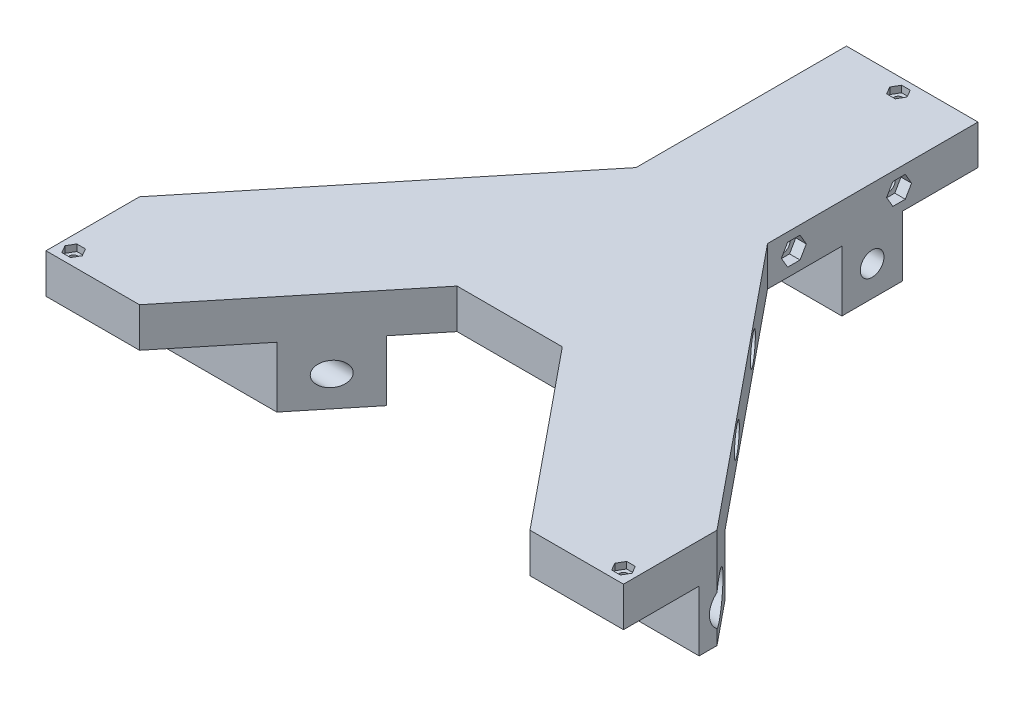
SolidWorks part; units mm, degrees
ref_plane "Front Plane" through (0, 0, 0) normal (0, 0, 1) x (1, 0, 0)
ref_plane "Top Plane" through (0, 0, 0) normal (0, 1, 0) x (1, 0, 0)
ref_plane "Right Plane" through (0, 0, 0) normal (1, 0, 0) x (0, 0, -1)
sketch "Sketch1" plane through (0, 0, 0) normal (0, 1, 0) x (1, 0, 0)
  line L0 (0, 0) -> (0, 143741.8209) construction
  line L1 (25, 0) -> (-25, 0)
  line L2 (-25, 0) -> (-25, -80)
  line L3 (25, 0) -> (25, -80)
  line L4 (-25, -80) -> (-109.75, -183.9619)
  line L5 (25, -80) -> (109.75, -183.9619)
  line L6 (-109.75, -183.9619) -> (-109.75, -219.5)
  line L7 (109.75, -183.9619) -> (109.75, -219.5)
  line L8 (-109.75, -219.5) -> (-74.2119, -219.5)
  line L9 (109.75, -219.5) -> (74.2119, -219.5)
  line L10 (-74.2119, -219.5) -> (-20, -152.9988)
  line L11 (74.2119, -219.5) -> (20, -152.9988)
  line L12 (-20, -152.9988) -> (20, -152.9988)
  point P6 (0, 0)
  point P16 (0, -152.9988)
  point P17 (82.4843, -217.5)
  point P18 (25.4247, -96.6746)
  point P19 (28.6457, -80.0329)
  point P20 (34.5508, -158.9467)
  point P21 (-30, -75.5085)
  point P22 (25, -66.3731)
  point P23 (19.1505, -153.0497)
  dimension "D1" = 219.5
  dimension "D2" = 219.5
  dimension "D3" = 50
  dimension "D4" = 50
  dimension "D5" = 80
  dimension "D6" = 40
extrude "Boss-Extrude1" add sketch "Sketch1" along normal blind 15
sketch "Sketch4" plane through (-109.75, 0, 0) normal (-1, 0, 0) x (0, 0, 1)
  line L0 (0, 15) -> (0, 0) construction
  line L1 (80, 15) -> (80, 0) construction
  line L2 (152.9988, 15) -> (152.9988, 0) construction
  circle A0 centre (30, 7.5) radius 2.55
  circle A1 centre (70, 7.5) radius 2.55
  circle A2 centre (110, 7.5) radius 2.55
  circle A3 centre (142.9988, 7.5) radius 2.55
  point P10 (0, 7.5)
  dimension "D1" = 5.1
  dimension "D2" = 30
  dimension "D3" = 10
  dimension "D4" = 30
  dimension "D5" = 10
extrude "Cut-Extrude1" cut sketch "Sketch4" against normal through all
sketch "Sketch5" plane through (-25, 0, 0) normal (-1, 0, 0) x (0, 0, 1)
  circle A0 centre (30, 7.5) radius 4.25
  circle A1 centre (70, 7.5) radius 4.25
  circle A2 centre (110, 7.5) radius 4.25
  circle A3 centre (142.9988, 7.5) radius 4.25
  dimension "D1" = 8.5
extrude "Cut-Extrude3" cut sketch "Sketch5" against normal blind 3.5 and the other way through all
sketch "Sketch6" plane through (25, 0, 0) normal (1, 0, 0) x (0, 0, -1)
  circle A0 centre (-142.9988, 7.5) radius 5
  circle A1 centre (-110, 7.5) radius 5
  dimension "D1" = 10
  dimension "D2" = 10
extrude "Cut-Extrude4" cut sketch "Sketch6" along normal through all
sketch "Sketch7" plane through (25, 0, 0) normal (1, 0, 0) x (0, 0, -1)
  line L1 (-34.7343, 7.5) -> (-32.3671, 3.4)
  line L2 (-32.3671, 3.4) -> (-27.6329, 3.4)
  line L3 (-27.6329, 3.4) -> (-25.2657, 7.5)
  line L4 (-25.2657, 7.5) -> (-27.6329, 11.6)
  line L5 (-27.6329, 11.6) -> (-32.3671, 11.6)
  line L6 (-32.3671, 11.6) -> (-34.7343, 7.5)
  line L7 (-74.7343, 7.5) -> (-72.3671, 3.4)
  line L8 (-72.3671, 3.4) -> (-67.6329, 3.4)
  line L9 (-67.6329, 3.4) -> (-65.2657, 7.5)
  line L10 (-65.2657, 7.5) -> (-67.6329, 11.6)
  line L11 (-67.6329, 11.6) -> (-72.3671, 11.6)
  line L12 (-72.3671, 11.6) -> (-74.7343, 7.5)
  line L13 (-114.7343, 7.5) -> (-112.3671, 3.4)
  line L14 (-112.3671, 3.4) -> (-107.6329, 3.4)
  line L15 (-107.6329, 3.4) -> (-105.2657, 7.5)
  line L16 (-105.2657, 7.5) -> (-107.6329, 11.6)
  line L17 (-107.6329, 11.6) -> (-112.3671, 11.6)
  line L18 (-112.3671, 11.6) -> (-114.7343, 7.5)
  line L19 (-147.7331, 7.5) -> (-145.366, 3.4)
  line L20 (-145.366, 3.4) -> (-140.6317, 3.4)
  line L21 (-140.6317, 3.4) -> (-138.2646, 7.5)
  line L22 (-138.2646, 7.5) -> (-140.6317, 11.6)
  line L23 (-140.6317, 11.6) -> (-145.366, 11.6)
  line L24 (-145.366, 11.6) -> (-147.7331, 7.5)
  circle A0 centre (-30, 7.5) radius 4.1 construction
  circle A1 centre (-70, 7.5) radius 4.1 construction
  circle A2 centre (-110, 7.5) radius 4.1 construction
  circle A3 centre (-142.9988, 7.5) radius 4.1 construction
  point P28 (0, 0)
  point P37 (0, 0)
  point P38 (0, 0)
  dimension "D1" = 8.2
extrude "Cut-Extrude5" cut sketch "Sketch7" against normal blind 4
sketch "Sketch8" plane through (0, 15, 0) normal (0, 1, 0) x (1, 0, 0)
  line L0 (25, 0) -> (-25, 0) construction
  line L1 (-109.75, -219.5) -> (-74.2119, -219.5) construction
  line L3 (-109.75, -183.9619) -> (-109.75, -219.5) construction
  line L4 (109.75, -219.5) -> (109.75, -183.9619) construction
  circle A0 centre (0, -5.25) radius 1.6
  circle A1 centre (-104.5, -214.25) radius 1.6
  circle A2 centre (104.5, -214.25) radius 1.6
  point P13 (0, 0)
  point P15 (0, 0)
  dimension "D1" = 3.2
  dimension "D3" = 5.25
  dimension "D2" = 5.25
  dimension "D4" = 5.25
  dimension "D5" = 5.25
extrude "Cut-Extrude6" cut sketch "Sketch8" against normal through all
sketch "Sketch9" plane through (0, 15, 0) normal (0, 1, 0) x (1, 0, 0)
  line L1 (-101.2091, -214.25) -> (-102.8546, -211.4)
  line L2 (-102.8546, -211.4) -> (-106.1454, -211.4)
  line L3 (-106.1454, -211.4) -> (-107.7909, -214.25)
  line L4 (-107.7909, -214.25) -> (-106.1454, -217.1)
  line L5 (-106.1454, -217.1) -> (-102.8546, -217.1)
  line L6 (-102.8546, -217.1) -> (-101.2091, -214.25)
  line L7 (101.2091, -214.25) -> (102.8546, -217.1)
  line L8 (102.8546, -217.1) -> (106.1454, -217.1)
  line L9 (106.1454, -217.1) -> (107.7909, -214.25)
  line L10 (107.7909, -214.25) -> (106.1454, -211.4)
  line L11 (106.1454, -211.4) -> (102.8546, -211.4)
  line L12 (102.8546, -211.4) -> (101.2091, -214.25)
  line L13 (3.2909, -5.25) -> (1.6454, -2.4)
  line L14 (1.6454, -2.4) -> (-1.6454, -2.4)
  line L15 (-1.6454, -2.4) -> (-3.2909, -5.25)
  line L16 (-3.2909, -5.25) -> (-1.6454, -8.1)
  line L17 (-1.6454, -8.1) -> (1.6454, -8.1)
  line L18 (1.6454, -8.1) -> (3.2909, -5.25)
  circle A0 centre (-104.5, -214.25) radius 2.85 construction
  circle A1 centre (104.5, -214.25) radius 2.85 construction
  circle A2 centre (0, -5.25) radius 2.85 construction
  point P1 (0, 0)
  dimension "D1" = 5.7
  dimension "D2" = 5.7
  dimension "D3" = 5.7
extrude "Cut-Extrude7" cut sketch "Sketch9" against normal blind 2.5
sketch "Sketch10" plane through (0, 0, 0) normal (0, -1, 0) x (1, 0, 0)
  line L0 (6.2244, 40.25) -> (-49993.7756, 40.25) construction
  line L1 (84.4314, 179.25) -> (-49915.5686, 179.25) construction
  line L2 (7.3106, 36.25) -> (-49992.6894, 36.25) construction
  line L3 (6.2244, 44.25) -> (-49993.7756, 44.25) construction
  line L4 (67.052, 175.25) -> (-49932.948, 175.25) construction
  line L5 (77.9141, 183.25) -> (-49922.0859, 183.25) construction
  line L6 (25, 0) -> (-25, 0) construction
  line L7 (74.2119, 219.5) -> (109.75, 219.5) construction
  line L8 (-25, 0) -> (-25, 80) construction
  line L9 (25, 51.75) -> (-25, 51.75)
  line L10 (25, 51.75) -> (25, 28.75)
  line L11 (25, 28.75) -> (-25, 28.75)
  line L12 (-25, 51.75) -> (-25, 28.75)
  line L13 (25, 51.75) -> (-25, 28.75) construction
  line L14 (25, 28.75) -> (-25, 51.75) construction
  line L15 (25, 80) -> (25, 0) construction
  line L16 (96.534, 167.75) -> (32.0252, 167.75)
  line L17 (109.75, 183.9619) -> (25, 80) construction
  line L18 (20, 152.9988) -> (74.2119, 219.5) construction
  line L19 (32.0252, 167.75) -> (50.7748, 190.75)
  line L20 (50.7748, 190.75) -> (109.75, 190.75)
  line L21 (109.75, 219.5) -> (109.75, 183.9619) construction
  line L22 (109.75, 190.75) -> (109.75, 183.9619)
  line L23 (109.75, 183.9619) -> (96.534, 167.75)
  line L24 (0, 0) -> (0, -50000) construction
  line L25 (-109.75, 190.75) -> (-109.75, 183.9619)
  line L26 (-50.7748, 190.75) -> (-109.75, 190.75)
  line L27 (-32.0252, 167.75) -> (-50.7748, 190.75)
  line L28 (-96.534, 167.75) -> (-32.0252, 167.75)
  line L29 (-109.75, 183.9619) -> (-96.534, 167.75)
  point P16 (0, 40.25)
  dimension "D1" = 40.25
  dimension "D2" = 40.25
  dimension "D3" = 4
  dimension "D4" = 4
  dimension "D5" = 4
  dimension "D6" = 4
  dimension "D7" = 23
  dimension "D8" = 23
  dimension "D9" = 11.5
extrude "Boss-Extrude2" add sketch "Sketch10" along normal blind 23
ref_plane "Plane1" through (-96.534, 0, 0) normal (-1, 0, 0) x (0, 0, 1)
sketch "Sketch11" plane through (-96.534, 0, 0) normal (-1, 0, 0) x (0, 0, 1)
  line L0 (167.75, -23) -> (167.75, 0) construction
  line L1 (183.9619, -23) -> (167.75, -23) construction
  circle A0 centre (179.25, -11.5) radius 7.6
  point P6 (176.6753, -17.2283)
  dimension "D2" = 11.5
  dimension "D3" = 15.2
  dimension "D1" = 11.5
extrude "Cut-Extrude8" cut sketch "Sketch11" against normal blind 24 and the other way through all
sketch "Sketch12" plane through (-96.534, 0, 0) normal (-1, 0, 0) x (0, 0, 1)
  circle A0 centre (179.25, -11.5) radius 4.5
  dimension "D1" = 9
extrude "Cut-Extrude9" cut sketch "Sketch12" against normal through all
mirror "Mirror1" about plane through (0, 0, 0) normal (1, 0, 0) of "Cut-Extrude8"
sketch "Sketch13" plane through (-25, 0, 0) normal (-1, 0, 0) x (0, 0, 1)
  line L0 (51.75, -23) -> (28.75, -23) construction
  line L1 (28.75, -23) -> (28.75, 0) construction
  circle A0 centre (40.25, -11.5) radius 4.5
  point P2 (0, 0)
  dimension "D1" = 9
  dimension "D2" = 11.5
  dimension "D3" = 11.5
extrude "Cut-Extrude10" cut sketch "Sketch13" against normal through all
